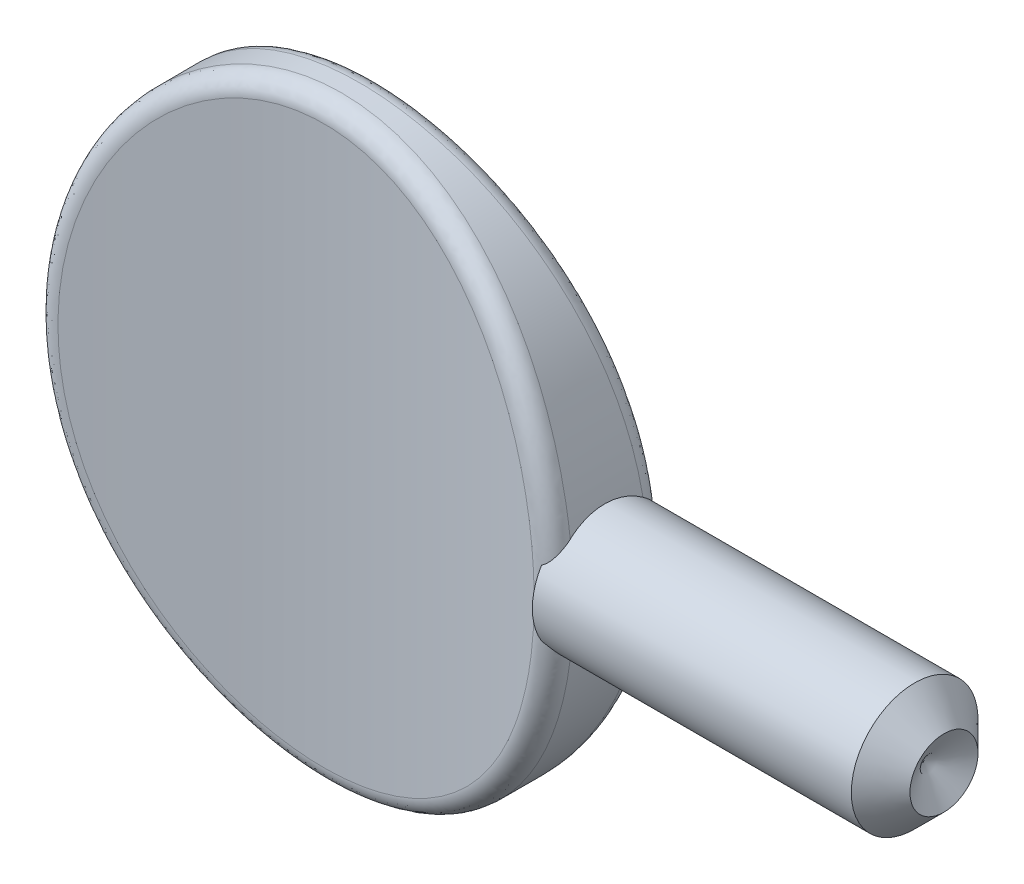
SolidWorks part; units mm, degrees
ref_plane "Front" through (0, 0, 0) normal (0, 0, 1) x (1, 0, 0)
ref_plane "Top" through (0, 0, 0) normal (0, 1, 0) x (1, 0, 0)
ref_plane "Right" through (0, 0, 0) normal (1, 0, 0) x (0, 0, -1)
ref_axis "Axis1" through (-50, 0, 0) along (1, 0, 0)
sketch "Sketch1" plane through (0, 0, 0) normal (0, 0, 1) x (1, 0, 0)
  line L0 (0, 0) -> (22.606, 0) construction
  line L1 (13.208, -2.413) -> (13.208, 2.413)
  line L2 (13.208, -2.413) -> (9.6776, -2.413) construction
  ellipse E0 centre (0, 0) end of major axis (0, -11.303) minor radius 9.906
  dimension "D2" = 3.302
  dimension "B" = 19.812
  dimension "L" = 12.7
extrude "Extrude1" add sketch "Sketch1" along normal mid plane 4.572
sketch "Sketch2" plane through (0, 0, 0) normal (0, 1, 0) x (1, 0, 0)
  line L0 (9.906, 2.286) -> (-9.906, 2.286) construction
  line L1 (0, 0) -> (0, 1.1721) construction
  line L2 (-1.7991, 0) -> (2.0444, 0) construction
  line L3 (-9.906, -2.286) -> (9.906, -2.286) construction
  line L6 (-9.906, 2.286) -> (-9.906, -2.286)
  line L7 (9.906, 2.286) -> (9.906, -2.286)
  arc A0 (-9.906, 2.286) -> (9.906, 2.286) centre (0, 40.2844) ccw
  arc A1 (-9.906, -2.286) -> (9.906, -2.286) centre (0, -40.2844) cw
extrude "Cut-Extrude1" cut sketch "Sketch2" against normal through all and the other way through all flip side to cut
fillet "Fillet3" radius 0.6773 2 edges at (-9.9037, -0.2444, 2.2854) (2.9825, 10.7785, -1.1294)
sketch "Sketch3" plane through (0, 0, 0) normal (0, 1, 0) x (1, 0, 0)
  line L0 (21.4884, 2.413) -> (22.606, 1.2954)
  line L1 (0, 0) -> (21.0288, 0) construction
  line L2 (0, 0) -> (22.606, 0) construction
  line L3 (13.208, 2.413) -> (13.208, 0) construction
  line L4 (13.208, 2.413) -> (21.4884, 2.413)
  line L5 (22.606, 1.2954) -> (21.8276, 0)
  line L6 (13.208, 2.413) -> (9.3367, 2.413)
  line L7 (9.0722, 2.0783) -> (9.0722, 0)
  line L8 (9.3367, 0) -> (9.3367, 2.413) construction
  line L9 (9.0722, 0) -> (21.8276, 0)
  arc A0 (9.3367, 2.413) -> (9.0722, 2.0783) centre (8.9927, 2.413) cw
  arc A3 (-9.906, 2.286) -> (9.906, 2.286) centre (0, 40.2844) ccw construction
  dimension "D1" = 45
  dimension "D2" = 59
revolve "Revolve1" add sketch "Sketch3" angle 360 about L0
cosmetic thread "Cosmetic Thread1" [suppressed]
sketch "Sketch4" plane through (0, 0, 0) normal (0, 0, 1) x (1, 0, 0)
  line L0 (0, 0) -> (27.7993, 0) construction
  line L1 (21.3051, 2.413) -> (21.4884, 2.0955)
  line L2 (21.4884, 2.0955) -> (21.6717, 2.413)
  line L3 (21.6717, 2.413) -> (21.6717, 2.7796)
  line L4 (21.6717, 2.7796) -> (21.3051, 2.7796)
  line L5 (21.3051, 2.7796) -> (21.3051, 2.413)
  line L6 (21.4884, 2.413) -> (21.4884, -2.413) construction
  dimension "D1" = 4.191
  dimension "D2" = 4.826
revolve "Cut-Revolve10" [suppressed] cut sketch "Sketch4" angle 360 about L0
pattern_linear "LPattern10" [suppressed] count 23 along (-1, 0, 0) of bodies 109
equation "\"D2@Sketch1\" = \"B@Sketch1\" / 6"
equation "\"D1@Fillet3\" = \"C1@Sketch2\" / 3"
equation "\"DIA@Sketch3\" = \"D@Sketch1\""
equation "\"D1@Cosmetic Thread1\" = \"L@Sketch1\" -  ( \"D@Sketch1\" - \"cup_dia@Sketch3\" )  / 2"
equation "\"D1@Sketch4\" = \"D2@Cosmetic Thread1\""
equation "\"D2@Sketch4\" = \"DIA@Sketch3\""
equation "\"D1@LPattern10\" = \"D1@Cosmetic Thread1\" / \"P@LPattern10\" "
